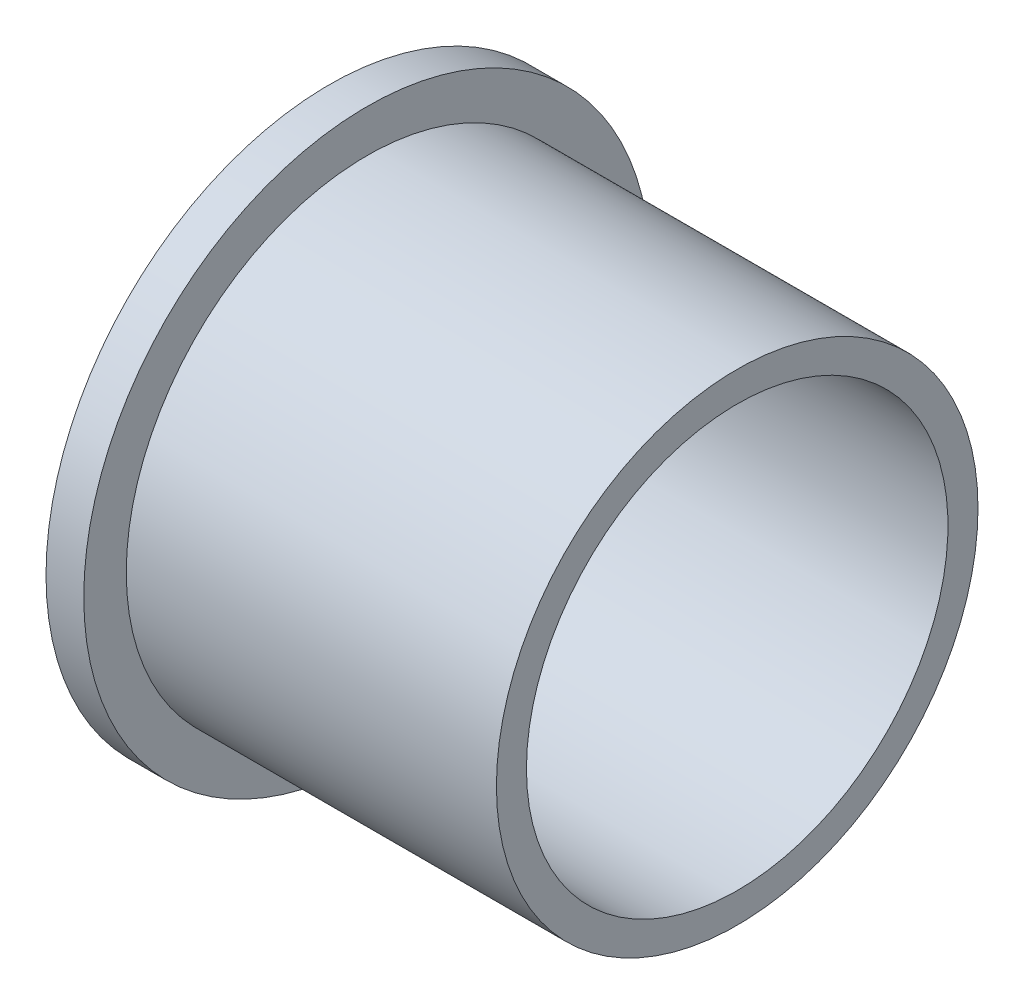
SolidWorks part; units mm, degrees
ref_plane "Front Plane" through (0, 0, 0) normal (0, 0, 1) x (1, 0, 0)
ref_plane "Top Plane" through (0, 0, 0) normal (0, 1, 0) x (1, 0, 0)
ref_plane "Right Plane" through (0, 0, 0) normal (1, 0, 0) x (0, 0, -1)
sketch "Revolve Sketch" plane through (0, 0, 0) normal (0, 0, 1) x (1, 0, 0)
  line L0 (0, 190.5) -> (0, 141.732)
  line L1 (0, 141.732) -> (274.32, 141.732)
  line L2 (274.32, 141.732) -> (274.32, 161.925)
  line L3 (274.32, 161.925) -> (25.4, 161.925)
  line L4 (25.4, 161.925) -> (25.4, 190.5)
  line L5 (25.4, 190.5) -> (0, 190.5)
  line L6 (0, 0) -> (97.8064, 0) construction
  dimension "D1" = 141.732
  dimension "D2" = 161.925
  dimension "D3" = 190.5
  dimension "D4" = 25.4
  dimension "D5" = 274.32
revolve "Revolve Body" add sketch "Revolve Sketch" angle 360 about L6
equation "\"ID\"= 11.160in'for 12 NOM (EPG)"
equation "\"OD\"= 12.75'for 12 NOM (EPG)"
equation "\"A\"= 10.8in'refer to EPG datasheet"
equation "\"T\"= 1in'refer to EPG datasheet"
equation "\"C\"= 15in'refer to EPG datasheet"
equation "\"D1@Revolve Sketch\" = \"ID\" / 2"
equation "\"D2@Revolve Sketch\" = \"OD\" / 2"
equation "\"D3@Revolve Sketch\" = \"C\" / 2"
equation "\"D4@Revolve Sketch\" = \"T\""
equation "\"D5@Revolve Sketch\" = \"A\""
